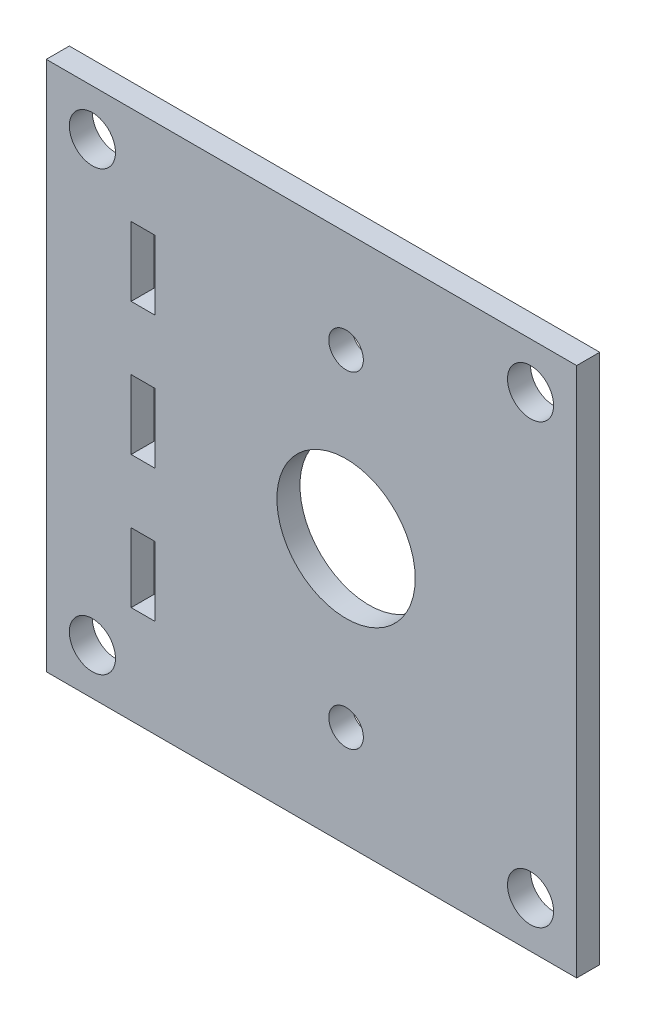
SolidWorks part; units mm, degrees
ref_plane "Front Plane" through (0, 0, 0) normal (0, 0, 1) x (1, 0, 0)
ref_plane "Top Plane" through (0, 0, 0) normal (0, 1, 0) x (1, 0, 0)
ref_plane "Right Plane" through (0, 0, 0) normal (1, 0, 0) x (0, 0, -1)
sketch "Sketch1" plane through (0, 0, 0) normal (0, 0, 1) x (1, 0, 0)
  line L0 (0, 73.025) -> (0, -73.025) construction
  line L1 (63.5, 73.025) -> (-82.55, 73.025)
  line L2 (63.5, 73.025) -> (63.5, -73.025)
  line L3 (63.5, -73.025) -> (-82.55, -73.025)
  line L4 (-82.55, 73.025) -> (-82.55, -73.025)
  line L5 (0, 45) -> (0, -45) construction
  line L6 (-55.88, 73.025) -> (-55.88, 36.5125) construction
  line L7 (-59.182, -9.525) -> (-52.578, -9.525)
  line L8 (-59.182, -9.525) -> (-59.182, 9.525)
  line L9 (-59.182, 9.525) -> (-52.578, 9.525)
  line L10 (-52.578, -9.525) -> (-52.578, 9.525)
  line L11 (-59.182, -9.525) -> (-52.578, 9.525) construction
  line L12 (-59.182, 9.525) -> (-52.578, -9.525) construction
  line L13 (-59.182, 46.0375) -> (-52.578, 46.0375)
  line L14 (-59.182, 46.0375) -> (-59.182, 26.9875)
  line L15 (-59.182, 26.9875) -> (-52.578, 26.9875)
  line L16 (-52.578, 46.0375) -> (-52.578, 26.9875)
  line L17 (-59.182, 46.0375) -> (-52.578, 26.9875) construction
  line L18 (-59.182, 26.9875) -> (-52.578, 46.0375) construction
  line L19 (-59.182, -26.9875) -> (-52.578, -26.9875)
  line L20 (-59.182, -26.9875) -> (-59.182, -46.0375)
  line L21 (-59.182, -46.0375) -> (-52.578, -46.0375)
  line L22 (-52.578, -26.9875) -> (-52.578, -46.0375)
  line L23 (-59.182, -26.9875) -> (-52.578, -46.0375) construction
  line L24 (-59.182, -46.0375) -> (-52.578, -26.9875) construction
  line L25 (-55.88, 36.5125) -> (-55.88, 0) construction
  line L26 (-55.88, 0) -> (-55.88, -36.5125) construction
  line L27 (-55.88, -36.5125) -> (-55.88, -73.025) construction
  circle A0 centre (50.8, 60.325) radius 6.35
  circle A1 centre (50.8, -60.325) radius 6.35
  circle A2 centre (0, 0) radius 19.05
  circle A3 centre (0, 45) radius 4.7625
  circle A4 centre (0, -45) radius 4.7625
  circle A5 centre (-69.85, 60.325) radius 6.35
  circle A6 centre (-69.85, -60.325) radius 6.35
  point P0 (0, 0)
  point P14 (0, 0)
  point P19 (0, 0)
  point P24 (-55.88, 36.5125)
  point P28 (-55.88, 0)
  point P34 (-55.88, -36.5125)
  dimension "D2" = 12.7
  dimension "D6" = 38.1
  dimension "D8" = 9.525
  dimension "D1" = 146.05
  dimension "D3" = 12.7
  dimension "D4" = 12.7
  dimension "D5" = 50.8
  dimension "D7" = 90
  dimension "D9" = 12.7
  dimension "D10" = 82.55
  dimension "D11" = 12.7
  dimension "D12" = 19.05
  dimension "D13" = 6.604
  dimension "D14" = 55.88
extrude "Boss-Extrude1" add sketch "Sketch1" along normal mid plane 6.35
